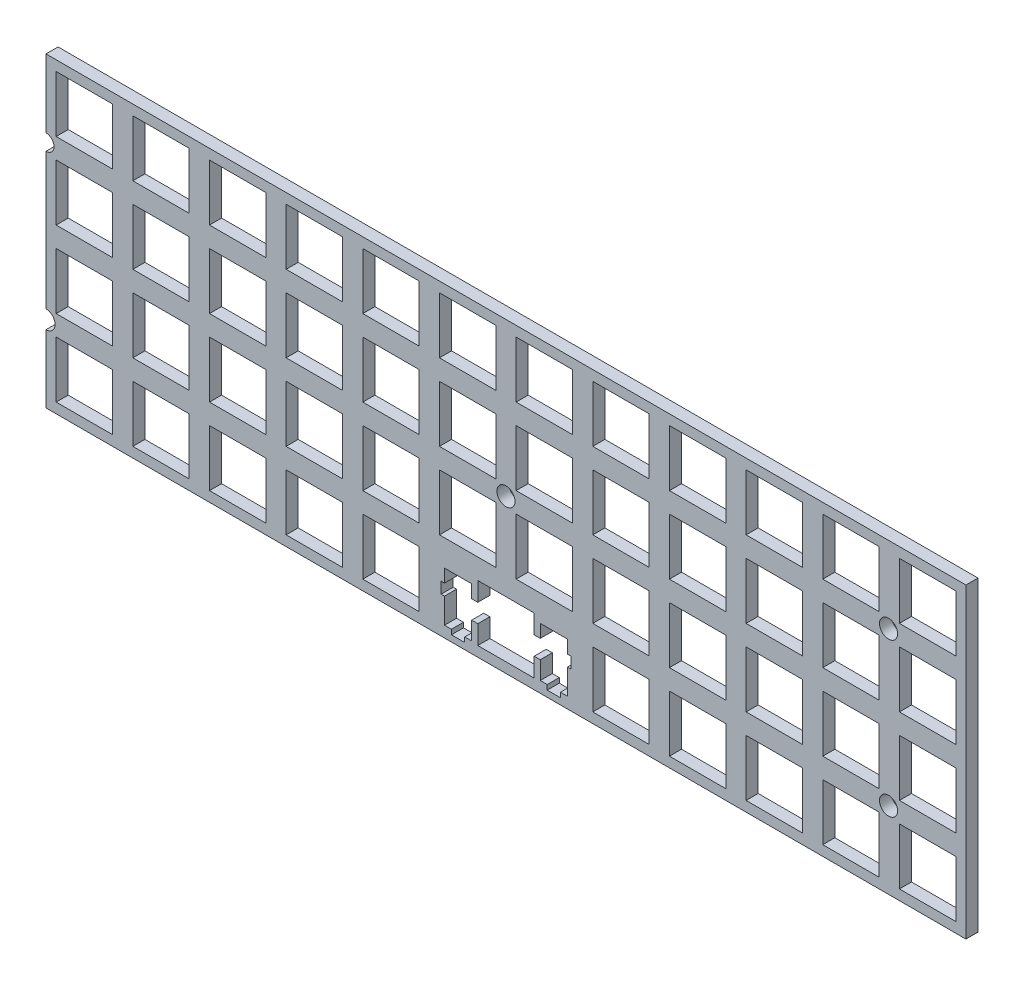
SolidWorks part; units mm, degrees
material "EPDM 60 Durometer"
ref_plane "Front Plane" through (0, 0, 0) normal (0, 0, 1) x (1, 0, 0)
ref_plane "Top Plane" through (0, 0, 0) normal (0, 1, 0) x (1, 0, 0)
ref_plane "Right Plane" through (0, 0, 0) normal (1, 0, 0) x (0, 0, -1)
sketch "Model" plane through (0, 0, 0) normal (0, 0, 1) x (1, 0, 0)
  line L0 (0.0951, 76.4575) -> (228.695, 76.4575)
  line L1 (228.695, 76.4575) -> (228.695, 0.2577)
  line L2 (228.695, 0.2577) -> (0.0951, 0.2577)
  line L3 (0.0951, 0.2577) -> (0.0951, 76.4575)
  line L4 (107.395, 16.7831) -> (107.395, 12.0826)
  line L5 (107.395, 12.0826) -> (105.869, 12.0826)
  line L6 (105.869, 12.0826) -> (105.869, 15.3128)
  line L7 (105.869, 15.3128) -> (99.1182, 15.3128)
  line L8 (99.1182, 15.3128) -> (99.1182, 12.0826)
  line L9 (99.1182, 12.0826) -> (98.2941, 12.0826)
  line L10 (98.2941, 12.0826) -> (98.2941, 9.2838)
  line L11 (98.2941, 9.2838) -> (99.1182, 9.2838)
  line L12 (99.1182, 9.2838) -> (99.1182, 3.0138)
  line L13 (99.1182, 3.0138) -> (100.845, 3.0138)
  line L14 (100.845, 3.0138) -> (100.845, 1.8135)
  line L15 (100.845, 1.8135) -> (104.144, 1.8135)
  line L16 (104.144, 1.8135) -> (104.144, 3.0138)
  line L17 (104.144, 3.0138) -> (105.869, 3.0138)
  line L18 (105.869, 3.0138) -> (105.869, 7.4827)
  line L19 (105.869, 7.4827) -> (107.395, 7.4827)
  line L20 (107.395, 7.4827) -> (107.395, 2.7836)
  line L21 (107.395, 2.7836) -> (121.394, 2.7836)
  line L22 (121.394, 2.7836) -> (121.394, 7.4827)
  line L23 (121.394, 7.4827) -> (122.92, 7.4827)
  line L24 (122.92, 7.4827) -> (122.92, 3.0138)
  line L25 (122.92, 3.0138) -> (124.645, 3.0138)
  line L26 (124.645, 3.0138) -> (124.645, 1.8135)
  line L27 (124.645, 1.8135) -> (127.944, 1.8135)
  line L28 (127.944, 1.8135) -> (127.944, 3.0138)
  line L29 (127.944, 3.0138) -> (129.669, 3.0138)
  line L30 (129.669, 3.0138) -> (129.669, 9.2838)
  line L31 (129.669, 9.2838) -> (130.495, 9.2838)
  line L32 (130.495, 9.2838) -> (130.495, 12.0826)
  line L33 (130.495, 12.0826) -> (129.669, 12.0826)
  line L34 (129.669, 12.0826) -> (129.669, 15.3128)
  line L35 (129.669, 15.3128) -> (122.92, 15.3128)
  line L36 (122.92, 15.3128) -> (122.92, 12.0826)
  line L37 (122.92, 12.0826) -> (121.394, 12.0826)
  line L38 (121.394, 12.0826) -> (121.394, 16.7831)
  line L39 (121.394, 16.7831) -> (107.395, 16.7831)
  line L40 (2.6197, 16.7831) -> (16.6192, 16.7831)
  line L41 (16.6192, 16.7831) -> (16.6192, 2.7836)
  line L42 (16.6192, 2.7836) -> (2.6197, 2.7836)
  line L43 (2.6197, 2.7836) -> (2.6197, 16.7831)
  line L44 (21.6697, 16.7831) -> (35.669, 16.7831)
  line L45 (35.669, 16.7831) -> (35.669, 2.7836)
  line L46 (35.669, 2.7836) -> (21.6697, 2.7836)
  line L47 (21.6697, 2.7836) -> (21.6697, 16.7831)
  line L48 (40.7197, 16.7831) -> (54.719, 16.7831)
  line L49 (54.719, 16.7831) -> (54.719, 2.7836)
  line L50 (54.719, 2.7836) -> (40.7197, 2.7836)
  line L51 (40.7197, 2.7836) -> (40.7197, 16.7831)
  line L52 (59.7697, 16.7831) -> (73.769, 16.7831)
  line L53 (73.769, 16.7831) -> (73.769, 2.7836)
  line L54 (73.769, 2.7836) -> (59.7697, 2.7836)
  line L55 (59.7697, 2.7836) -> (59.7697, 16.7831)
  line L56 (78.8197, 16.7831) -> (92.819, 16.7831)
  line L57 (92.819, 16.7831) -> (92.819, 2.7836)
  line L58 (92.819, 2.7836) -> (78.8197, 2.7836)
  line L59 (78.8197, 2.7836) -> (78.8197, 16.7831)
  line L60 (135.97, 16.7831) -> (149.969, 16.7831)
  line L61 (149.969, 16.7831) -> (149.969, 2.7836)
  line L62 (149.969, 2.7836) -> (135.97, 2.7836)
  line L63 (135.97, 2.7836) -> (135.97, 16.7831)
  line L64 (155.02, 16.7831) -> (169.019, 16.7831)
  line L65 (169.019, 16.7831) -> (169.019, 2.7836)
  line L66 (169.019, 2.7836) -> (155.02, 2.7836)
  line L67 (155.02, 2.7836) -> (155.02, 16.7831)
  line L68 (174.07, 16.7831) -> (188.069, 16.7831)
  line L69 (188.069, 16.7831) -> (188.069, 2.7836)
  line L70 (188.069, 2.7836) -> (174.07, 2.7836)
  line L71 (174.07, 2.7836) -> (174.07, 16.7831)
  line L72 (193.12, 16.7831) -> (207.119, 16.7831)
  line L73 (207.119, 16.7831) -> (207.119, 2.7836)
  line L74 (207.119, 2.7836) -> (193.12, 2.7836)
  line L75 (193.12, 2.7836) -> (193.12, 16.7831)
  line L76 (212.17, 16.7831) -> (226.169, 16.7831)
  line L77 (226.169, 16.7831) -> (226.169, 2.7836)
  line L78 (226.169, 2.7836) -> (212.17, 2.7836)
  line L79 (212.17, 2.7836) -> (212.17, 16.7831)
  line L80 (2.6197, 35.833) -> (16.6192, 35.833)
  line L81 (16.6192, 35.833) -> (16.6192, 21.8336)
  line L82 (16.6192, 21.8336) -> (2.6197, 21.8336)
  line L83 (2.6197, 21.8336) -> (2.6197, 35.833)
  line L84 (21.6697, 35.833) -> (35.669, 35.833)
  line L85 (35.669, 35.833) -> (35.669, 21.8336)
  line L86 (35.669, 21.8336) -> (21.6697, 21.8336)
  line L87 (21.6697, 21.8336) -> (21.6697, 35.833)
  line L88 (40.7197, 35.833) -> (54.719, 35.833)
  line L89 (54.719, 35.833) -> (54.719, 21.8336)
  line L90 (54.719, 21.8336) -> (40.7197, 21.8336)
  line L91 (40.7197, 21.8336) -> (40.7197, 35.833)
  line L92 (59.7697, 35.833) -> (73.769, 35.833)
  line L93 (73.769, 35.833) -> (73.769, 21.8336)
  line L94 (73.769, 21.8336) -> (59.7697, 21.8336)
  line L95 (59.7697, 21.8336) -> (59.7697, 35.833)
  line L96 (78.8197, 35.833) -> (92.819, 35.833)
  line L97 (92.819, 35.833) -> (92.819, 21.8336)
  line L98 (92.819, 21.8336) -> (78.8197, 21.8336)
  line L99 (78.8197, 21.8336) -> (78.8197, 35.833)
  line L100 (97.8683, 35.833) -> (111.869, 35.833)
  line L101 (111.869, 35.833) -> (111.869, 21.8336)
  line L102 (111.869, 21.8336) -> (97.8683, 21.8336)
  line L103 (97.8683, 21.8336) -> (97.8683, 35.833)
  line L104 (116.918, 35.833) -> (130.919, 35.833)
  line L105 (130.919, 35.833) -> (130.919, 21.8336)
  line L106 (130.919, 21.8336) -> (116.918, 21.8336)
  line L107 (116.918, 21.8336) -> (116.918, 35.833)
  line L108 (135.97, 35.833) -> (149.969, 35.833)
  line L109 (149.969, 35.833) -> (149.969, 21.8336)
  line L110 (149.969, 21.8336) -> (135.97, 21.8336)
  line L111 (135.97, 21.8336) -> (135.97, 35.833)
  line L112 (155.02, 35.833) -> (169.019, 35.833)
  line L113 (169.019, 35.833) -> (169.019, 21.8336)
  line L114 (169.019, 21.8336) -> (155.02, 21.8336)
  line L115 (155.02, 21.8336) -> (155.02, 35.833)
  line L116 (174.07, 35.833) -> (188.069, 35.833)
  line L117 (188.069, 35.833) -> (188.069, 21.8336)
  line L118 (188.069, 21.8336) -> (174.07, 21.8336)
  line L119 (174.07, 21.8336) -> (174.07, 35.833)
  line L120 (193.12, 35.833) -> (207.119, 35.833)
  line L121 (207.119, 35.833) -> (207.119, 21.8336)
  line L122 (207.119, 21.8336) -> (193.12, 21.8336)
  line L123 (193.12, 21.8336) -> (193.12, 35.833)
  line L124 (212.17, 35.833) -> (226.169, 35.833)
  line L125 (226.169, 35.833) -> (226.169, 21.8336)
  line L126 (226.169, 21.8336) -> (212.17, 21.8336)
  line L127 (212.17, 21.8336) -> (212.17, 35.833)
  line L128 (2.6197, 54.8831) -> (16.6192, 54.8831)
  line L129 (16.6192, 54.8831) -> (16.6192, 40.8838)
  line L130 (16.6192, 40.8838) -> (2.6197, 40.8838)
  line L131 (2.6197, 40.8838) -> (2.6197, 54.8831)
  line L132 (21.6697, 54.8831) -> (35.669, 54.8831)
  line L133 (35.669, 54.8831) -> (35.669, 40.8838)
  line L134 (35.669, 40.8838) -> (21.6697, 40.8838)
  line L135 (21.6697, 40.8838) -> (21.6697, 54.8831)
  line L136 (40.7197, 54.8831) -> (54.719, 54.8831)
  line L137 (54.719, 54.8831) -> (54.719, 40.8838)
  line L138 (54.719, 40.8838) -> (40.7197, 40.8838)
  line L139 (40.7197, 40.8838) -> (40.7197, 54.8831)
  line L140 (59.7697, 54.8831) -> (73.769, 54.8831)
  line L141 (73.769, 54.8831) -> (73.769, 40.8838)
  line L142 (73.769, 40.8838) -> (59.7697, 40.8838)
  line L143 (59.7697, 40.8838) -> (59.7697, 54.8831)
  line L144 (78.8197, 54.8831) -> (92.819, 54.8831)
  line L145 (92.819, 54.8831) -> (92.819, 40.8838)
  line L146 (92.819, 40.8838) -> (78.8197, 40.8838)
  line L147 (78.8197, 40.8838) -> (78.8197, 54.8831)
  line L148 (97.8683, 54.8831) -> (111.869, 54.8831)
  line L149 (111.869, 54.8831) -> (111.869, 40.8838)
  line L150 (111.869, 40.8838) -> (97.8683, 40.8838)
  line L151 (97.8683, 40.8838) -> (97.8683, 54.8831)
  line L152 (116.918, 54.8831) -> (130.919, 54.8831)
  line L153 (130.919, 54.8831) -> (130.919, 40.8838)
  line L154 (130.919, 40.8838) -> (116.918, 40.8838)
  line L155 (116.918, 40.8838) -> (116.918, 54.8831)
  line L156 (135.97, 54.8831) -> (149.969, 54.8831)
  line L157 (149.969, 54.8831) -> (149.969, 40.8838)
  line L158 (149.969, 40.8838) -> (135.97, 40.8838)
  line L159 (135.97, 40.8838) -> (135.97, 54.8831)
  line L160 (155.02, 54.8831) -> (169.019, 54.8831)
  line L161 (169.019, 54.8831) -> (169.019, 40.8838)
  line L162 (169.019, 40.8838) -> (155.02, 40.8838)
  line L163 (155.02, 40.8838) -> (155.02, 54.8831)
  line L164 (174.07, 54.8831) -> (188.069, 54.8831)
  line L165 (188.069, 54.8831) -> (188.069, 40.8838)
  line L166 (188.069, 40.8838) -> (174.07, 40.8838)
  line L167 (174.07, 40.8838) -> (174.07, 54.8831)
  line L168 (193.12, 54.8831) -> (207.119, 54.8831)
  line L169 (207.119, 54.8831) -> (207.119, 40.8838)
  line L170 (207.119, 40.8838) -> (193.12, 40.8838)
  line L171 (193.12, 40.8838) -> (193.12, 54.8831)
  line L172 (212.17, 54.8831) -> (226.169, 54.8831)
  line L173 (226.169, 54.8831) -> (226.169, 40.8838)
  line L174 (226.169, 40.8838) -> (212.17, 40.8838)
  line L175 (212.17, 40.8838) -> (212.17, 54.8831)
  line L176 (2.6197, 73.9331) -> (16.6192, 73.9331)
  line L177 (16.6192, 73.9331) -> (16.6192, 59.9338)
  line L178 (16.6192, 59.9338) -> (2.6197, 59.9338)
  line L179 (2.6197, 59.9338) -> (2.6197, 73.9331)
  line L180 (21.6697, 73.9331) -> (35.669, 73.9331)
  line L181 (35.669, 73.9331) -> (35.669, 59.9338)
  line L182 (35.669, 59.9338) -> (21.6697, 59.9338)
  line L183 (21.6697, 59.9338) -> (21.6697, 73.9331)
  line L184 (40.7197, 73.9331) -> (54.719, 73.9331)
  line L185 (54.719, 73.9331) -> (54.719, 59.9338)
  line L186 (54.719, 59.9338) -> (40.7197, 59.9338)
  line L187 (40.7197, 59.9338) -> (40.7197, 73.9331)
  line L188 (59.7697, 73.9331) -> (73.769, 73.9331)
  line L189 (73.769, 73.9331) -> (73.769, 59.9338)
  line L190 (73.769, 59.9338) -> (59.7697, 59.9338)
  line L191 (59.7697, 59.9338) -> (59.7697, 73.9331)
  line L192 (78.8197, 73.9331) -> (92.819, 73.9331)
  line L193 (92.819, 73.9331) -> (92.819, 59.9338)
  line L194 (92.819, 59.9338) -> (78.8197, 59.9338)
  line L195 (78.8197, 59.9338) -> (78.8197, 73.9331)
  line L196 (97.8683, 73.9331) -> (111.869, 73.9331)
  line L197 (111.869, 73.9331) -> (111.869, 59.9338)
  line L198 (111.869, 59.9338) -> (97.8683, 59.9338)
  line L199 (97.8683, 59.9338) -> (97.8683, 73.9331)
  line L200 (116.918, 73.9331) -> (130.919, 73.9331)
  line L201 (130.919, 73.9331) -> (130.919, 59.9338)
  line L202 (130.919, 59.9338) -> (116.918, 59.9338)
  line L203 (116.918, 59.9338) -> (116.918, 73.9331)
  line L204 (135.97, 73.9331) -> (149.969, 73.9331)
  line L205 (149.969, 73.9331) -> (149.969, 59.9338)
  line L206 (149.969, 59.9338) -> (135.97, 59.9338)
  line L207 (135.97, 59.9338) -> (135.97, 73.9331)
  line L208 (155.02, 73.9331) -> (169.019, 73.9331)
  line L209 (169.019, 73.9331) -> (169.019, 59.9338)
  line L210 (169.019, 59.9338) -> (155.02, 59.9338)
  line L211 (155.02, 59.9338) -> (155.02, 73.9331)
  line L212 (174.07, 73.9331) -> (188.069, 73.9331)
  line L213 (188.069, 73.9331) -> (188.069, 59.9338)
  line L214 (188.069, 59.9338) -> (174.07, 59.9338)
  line L215 (174.07, 59.9338) -> (174.07, 73.9331)
  line L216 (193.12, 73.9331) -> (207.119, 73.9331)
  line L217 (207.119, 73.9331) -> (207.119, 59.9338)
  line L218 (207.119, 59.9338) -> (193.12, 59.9338)
  line L219 (193.12, 59.9338) -> (193.12, 73.9331)
  line L220 (212.17, 73.9331) -> (226.169, 73.9331)
  line L221 (226.169, 73.9331) -> (226.169, 59.9338)
  line L222 (226.169, 59.9338) -> (212.17, 59.9338)
  line L223 (212.17, 59.9338) -> (212.17, 73.9331)
extrude "Boss-Extrude1" add sketch "Model" along normal blind 3
sketch "Sketch1" plane through (0, 0, 3) normal (0, 0, 1) x (1, 0, 0)
  line L0 (0.094, 59.451) -> (0.0944, 55.501)
  circle A10 centre (114.394, 38.401) radius 2.25 construction
  circle A11 centre (114.394, 38.401) radius 2.25
  circle A12 centre (209.464, 57.451) radius 2.25 construction
  circle A13 centre (209.464, 57.451) radius 2.25
  circle A14 centre (209.464, 19.351) radius 2.25 construction
  circle A15 centre (209.464, 19.351) radius 2.25
  circle A16 centre (0.094, 19.351) radius 2.25 construction
  circle A17 centre (0.094, 19.351) radius 2.25
  arc A18 (0.0944, 55.501) -> (0.094, 59.451) centre (0.1115, 57.476) ccw construction
  arc A19 (0.0944, 55.501) -> (0.094, 59.451) centre (0.1115, 57.476) ccw
  point P11 (0, 0)
  point P17 (0, 0)
extrude "Cut-Extrude1" cut sketch "Sketch1" against normal through all
